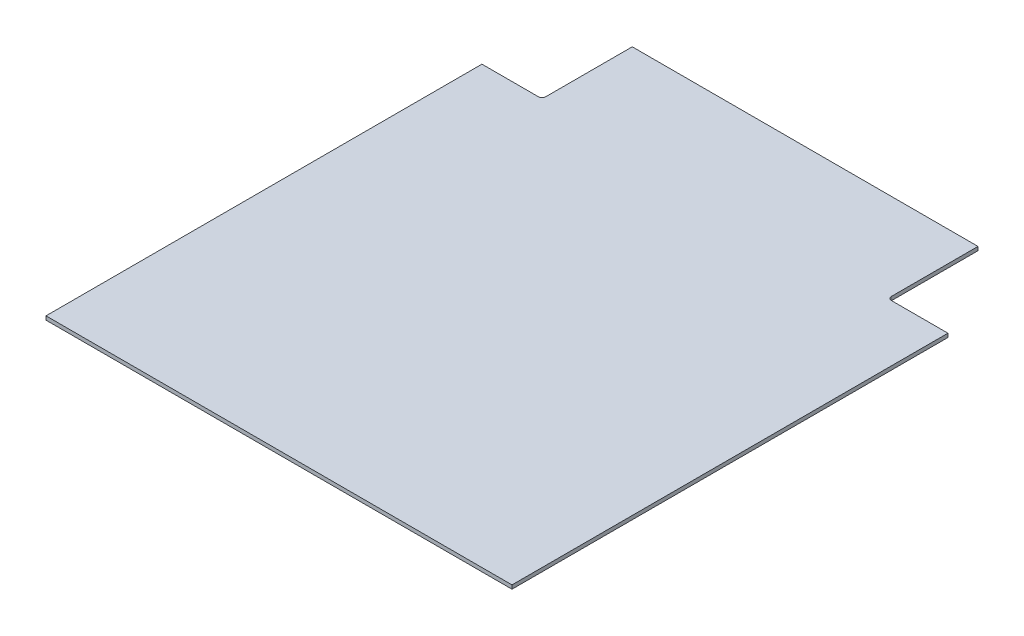
SolidWorks part; units mm, degrees
material "6061-T6 (SS)"
ref_plane "Front" through (0, 0, 0) normal (0, 0, 1) x (1, 0, 0)
ref_plane "Top" through (0, 0, 0) normal (0, 1, 0) x (1, 0, 0)
ref_plane "Right" through (0, 0, 0) normal (1, 0, 0) x (0, 0, -1)
sketch "Sketch1" plane through (0, 0, 0) normal (0, 1, 0) x (1, 0, 0)
  line L1 (196.85, -222.25) -> (-196.85, -222.25)
  line L2 (196.85, -222.25) -> (196.85, 222.25)
  line L3 (196.85, 222.25) -> (-196.85, 222.25)
  line L4 (-196.85, -222.25) -> (-196.85, 222.25)
  line L5 (196.85, -222.25) -> (-196.85, 222.25) construction
  line L6 (196.85, 222.25) -> (-196.85, -222.25) construction
  point P0 (0, 0)
  dimension "D1" = 393.7
  dimension "D2" = 444.5
extrude "Boss-Extrude1" add sketch "Sketch1" along normal blind 3.175
sketch "Sketch2" plane through (0, 3.175, 0) normal (0, 1, 0) x (1, 0, 0)
  line L0 (196.85, 222.25) -> (-196.85, 222.25) construction
  line L1 (-196.85, 222.25) -> (-146.05, 222.25)
  line L2 (-196.85, 222.25) -> (-196.85, 146.05)
  line L3 (-196.85, 146.05) -> (-149.225, 146.05)
  line L4 (-146.05, 222.25) -> (-146.05, 149.225)
  line L5 (196.85, 222.25) -> (146.05, 222.25)
  line L6 (196.85, 222.25) -> (196.85, 146.05)
  line L7 (196.85, 146.05) -> (149.225, 146.05)
  line L8 (146.05, 222.25) -> (146.05, 149.225)
  arc A0 (-146.05, 149.225) -> (-149.225, 146.05) centre (-149.225, 149.225) cw
  arc A1 (146.05, 149.225) -> (149.225, 146.05) centre (149.225, 149.225) ccw
  dimension "D1" = 3.175
  dimension "D2" = 76.2
  dimension "D3" = 50.8
extrude "Cut-Extrude1" cut sketch "Sketch2" against normal blind 10
